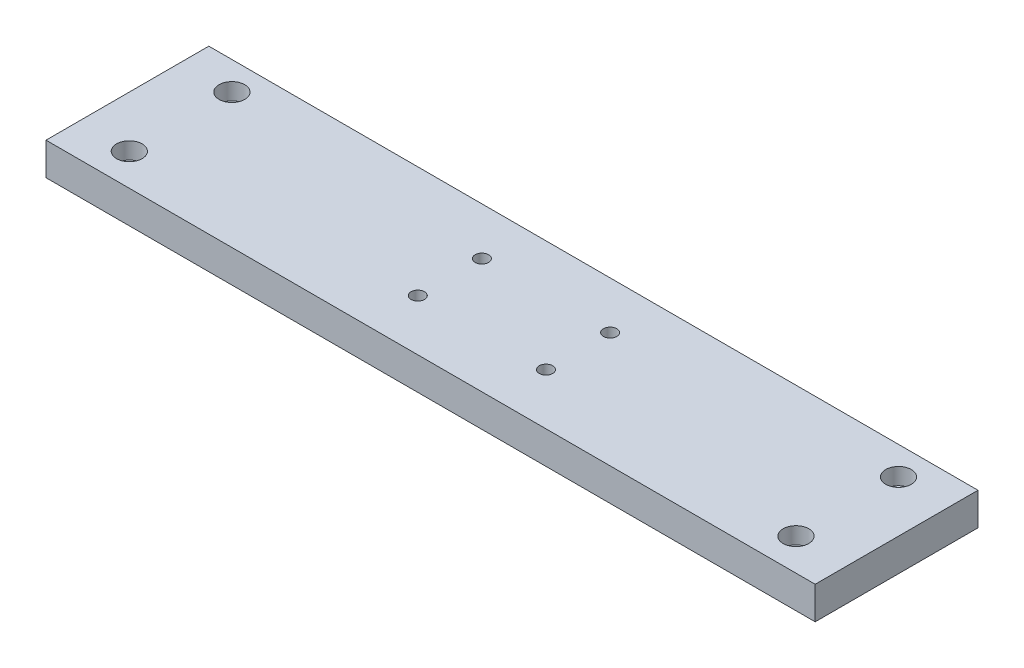
SolidWorks part; units mm, degrees
ref_plane "Front Plane" through (0, 0, 0) normal (0, 0, 1) x (1, 0, 0)
ref_plane "Top Plane" through (0, 0, 0) normal (0, 1, 0) x (1, 0, 0)
ref_plane "Right Plane" through (0, 0, 0) normal (1, 0, 0) x (0, 0, -1)
sketch "Sketch1" plane through (0, 0, 0) normal (0, 1, 0) x (1, 0, 0)
  line L1 (0, 0) -> (600, 0)
  line L2 (0, 0) -> (0, 127)
  line L3 (0, 127) -> (600, 127)
  line L4 (600, 0) -> (600, 127)
  dimension "D1" = 600
  dimension "D2" = 127
extrude "Boss-Extrude1" add sketch "Sketch1" along normal blind 25.4
sketch "Sketch2" plane through (0, 25.4, 0) normal (0, 1, 0) x (1, 0, 0)
  line L1 (0, 0) -> (300, 0)
  line L2 (0, 0) -> (0, 65)
  line L3 (0, 65) -> (300, 65)
  line L4 (300, 0) -> (300, 65)
  line L5 (40, 105) -> (560, 105)
  line L6 (40, 105) -> (40, 25)
  line L7 (40, 25) -> (560, 25)
  line L8 (560, 105) -> (560, 25)
  line L9 (40, 105) -> (560, 25) construction
  line L10 (40, 25) -> (560, 105) construction
  circle A0 centre (40, 105) radius 6
  circle A1 centre (40, 25) radius 6
  circle A2 centre (560, 25) radius 6
  circle A3 centre (560, 105) radius 6
  dimension "D1" = 300
  dimension "D2" = 65
  dimension "D3" = 520
  dimension "D4" = 80
extrude "Cut-Extrude1" cut sketch "Sketch2" against normal blind 25.4 contours A2 | A3 | A1 | A0
sketch "Sketch3" plane through (0, 25.4, 0) normal (0, 1, 0) x (1, 0, 0)
  line L1 (0, 0) -> (300, 0)
  line L2 (0, 0) -> (0, 65)
  line L3 (0, 65) -> (300, 65)
  line L4 (300, 0) -> (300, 65)
  line L5 (250, 90) -> (350, 90)
  line L6 (250, 90) -> (250, 40)
  line L7 (250, 40) -> (350, 40)
  line L8 (350, 90) -> (350, 40)
  line L9 (250, 90) -> (350, 40) construction
  line L10 (250, 40) -> (350, 90) construction
  circle A0 centre (250, 90) radius 5.25
  circle A1 centre (250, 40) radius 5.25
  circle A2 centre (350, 40) radius 5.25
  circle A3 centre (350, 90) radius 5.25
  dimension "D1" = 300
  dimension "D2" = 65
  dimension "D3" = 100
  dimension "D4" = 50
extrude "Cut-Extrude2" cut sketch "Sketch3" against normal blind 25.4 contours A0 | A1 | A2 | A3
sketch "Sketch4" plane through (0, 25.4, 0) normal (0, 1, 0) x (1, 0, 0)
  circle A1 centre (40, 105) radius 10
  circle A2 centre (40, 25) radius 10
  circle A3 centre (560, 25) radius 10
  circle A4 centre (560, 105) radius 10
extrude "Cut-Extrude3" cut sketch "Sketch4" against normal blind 13
